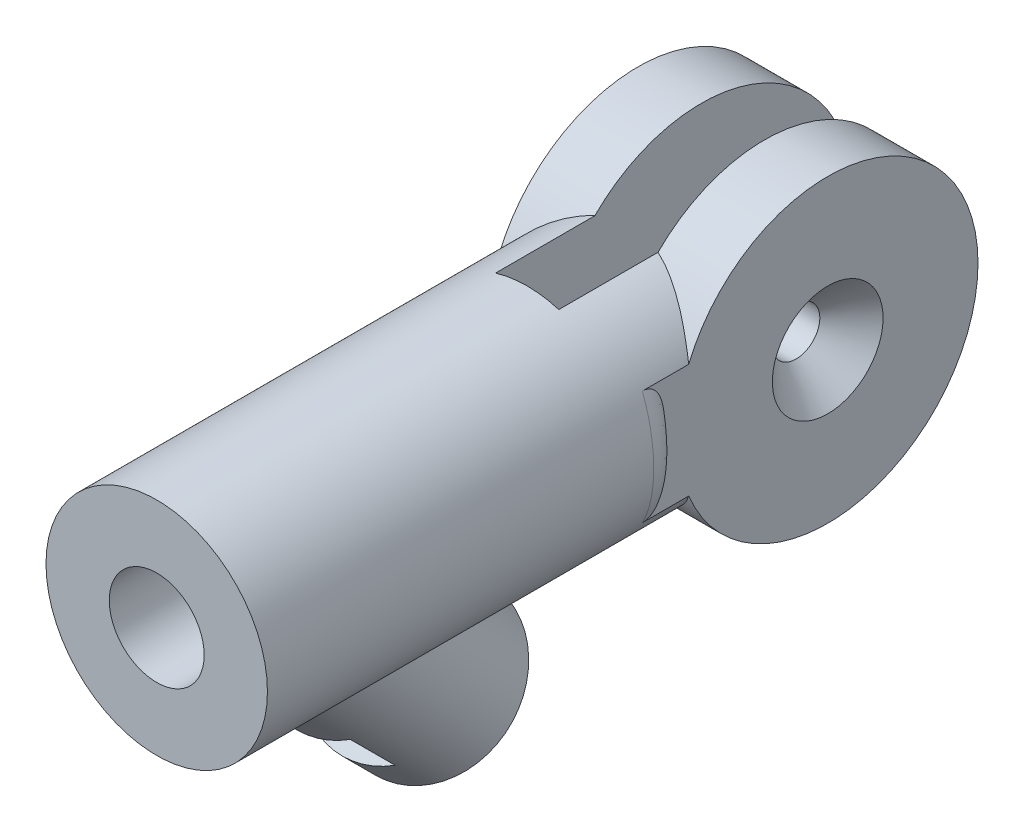
SolidWorks part; units mm, degrees
ref_plane "Спереди" through (0, 0, 0) normal (0, 0, 1) x (1, 0, 0)
ref_plane "Сверху" through (0, 0, 0) normal (0, 1, 0) x (1, 0, 0)
ref_plane "Справа" through (0, 0, 0) normal (1, 0, 0) x (0, 0, -1)
sketch "Sketch1" plane through (0, 0, 0) normal (0, 0, 1) x (1, 0, 0)
  circle A0 centre (0, 0) radius 3
  circle A1 centre (0, 0) radius 7
  dimension "D1" = 6
  dimension "D2" = 4
extrude "Boss-Extrude1" add sketch "Sketch1" along normal blind 30
sketch "Sketch2" plane through (0, 0, 0) normal (1, 0, 0) x (0, 0, -1)
  circle A0 centre (6.4226, 0) radius 9.5
  dimension "D1" = 19
extrude "Boss-Extrude2" add sketch "Sketch2" along normal mid plane 12
sketch "Sketch4" plane through (-6, 0, 0) normal (-1, 0, 0) x (0, 0, 1)
  circle A0 centre (-6.4226, 0) radius 1.5
  dimension "D1" = 3
extrude "Cut-Extrude1" cut sketch "Sketch4" against normal mid plane 34
sketch "Sketch5" plane through (6, 0, 0) normal (1, 0, 0) x (0, 0, -1)
  circle A0 centre (6.4226, 0) radius 10
extrude "Cut-Extrude2" cut sketch "Sketch5" along normal blind 31
sketch "Sketch6" plane through (-6, 0, 0) normal (-1, 0, 0) x (0, 0, 1)
  circle A0 centre (-6.4226, 0) radius 10
extrude "Cut-Extrude3" cut sketch "Sketch6" along normal blind 25
fillet "Fillet3" radius 2 2 edges at (6.9903, -0.3679, 3.5706) (-6.9903, 0.3679, 3.5706)
sketch "Sketch7" plane through (0, 0, 0) normal (1, 0, 0) x (0, 0, -1)
  line L1 (19.4226, -13) -> (-6.5774, -13)
  line L2 (19.4226, -13) -> (19.4226, 13)
  line L3 (19.4226, 13) -> (-6.5774, 13)
  line L4 (-6.5774, -13) -> (-6.5774, 13)
  line L5 (19.4226, -13) -> (-6.5774, 13) construction
  line L6 (19.4226, 13) -> (-6.5774, -13) construction
  point P0 (6.4226, 0)
  dimension "D1" = 26
extrude "Cut-Extrude4" cut sketch "Sketch7" against normal mid plane 4
sketch "Sketch8" plane through (0, 0, 0) normal (1, 0, 0) x (0, 0, -1)
  line L0 (-33.2006, 0) -> (-12.6296, 0) construction
  line L1 (-24.0906, 0) -> (-11.7886, -12.302) construction
  line L2 (-21.0906, -3) -> (-24.6262, -6.5355)
  line L3 (-24.6262, -6.5355) -> (-16.1409, -15.0208)
  line L4 (-16.1409, -15.0208) -> (-12.6053, -11.4853)
  line L5 (-12.6053, -11.4853) -> (-21.0906, -3)
  point P9 (0, 0)
  dimension "D1" = 45
  dimension "D2" = 5
  dimension "D3" = 12
  dimension "D4" = 3
revolve "Revolve1" add sketch "Sketch8" angle 360 about L1
sketch "Sketch9" plane through (0, 0.56, 0.56) normal (0, -0.7071, -0.7071) x (1, 0, 0)
  circle A0 centre (0, 17.0346) radius 1.5
  dimension "D1" = 3
extrude "Cut-Extrude5" cut sketch "Sketch9" against normal blind 15
sketch "Sketch10" plane through (0, 0, 30) normal (0, 0, 1) x (1, 0, 0)
  circle A0 centre (0, 0) radius 3
  dimension "D1" = 6
extrude "Cut-Extrude6" cut sketch "Sketch10" against normal blind 20
ref_plane "Plane1" through (0, 2.6814, 2.6814) normal (0, -0.7071, -0.7071) x (-1, 0, 0)
sketch "Sketch11" plane through (0, 2.6814, 2.6814) normal (0, -0.7071, -0.7071) x (-1, 0, 0)
  line L0 (-2.75, -18.6224) -> (-2.75, -33.867)
  line L1 (0, -13.8592) -> (-2.75, -15.4469)
  line L2 (-2.75, -15.4469) -> (-2.75, -18.6224)
  line L3 (-2.75, -18.6224) -> (0, -20.2101)
  line L4 (0, -20.2101) -> (2.75, -18.6224)
  line L5 (2.75, -18.6224) -> (2.75, -15.4469)
  line L6 (2.75, -15.4469) -> (0, -13.8592)
  line L7 (-2.75, -33.867) -> (2.75, -33.867)
  line L8 (2.75, -33.867) -> (2.75, -18.6224)
  circle A0 centre (0, -17.0346) radius 2.75 construction
  dimension "D1" = 5.5
extrude "Cut-Extrude7" cut sketch "Sketch11" against normal blind 3 contours L7 L8 L4 L3 L0 | L5 L6 L1 L2 L3 L4 region at (0, -16.152, 21.5147) region at (0, -9.364, 14.7267)
chamfer "Chamfer1" distance 1 angle 45 1 edges at (0, -10.7782, 20.3835)
chamfer "Chamfer2" distance 2 angle 45 2 edges at (-6, 0, -7.9226) (6, 0, -7.9226)
